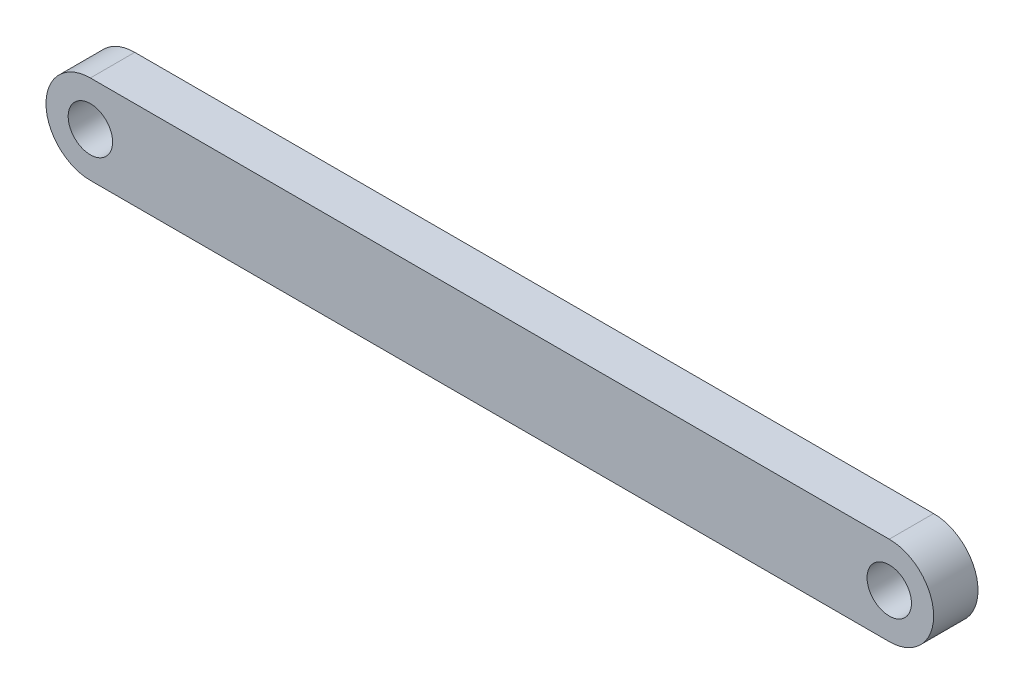
SolidWorks part; units mm, degrees
ref_plane "Front Plane" through (0, 0, 0) normal (0, 0, 1) x (1, 0, 0)
ref_plane "Top Plane" through (0, 0, 0) normal (0, 1, 0) x (1, 0, 0)
ref_plane "Right Plane" through (0, 0, 0) normal (1, 0, 0) x (0, 0, -1)
sketch "Sketch1" plane through (0, 0, 0) normal (0, 0, 1) x (1, 0, 0)
  line L0 (-22.86, 0) -> (22.86, 0) construction
  line L1 (-22.86, 2.54) -> (22.86, 2.54)
  line L2 (-22.86, -2.54) -> (22.86, -2.54)
  arc A0 (-22.86, 2.54) -> (-22.86, -2.54) centre (-22.86, 0) ccw
  arc A1 (22.86, -2.54) -> (22.86, 2.54) centre (22.86, 0) ccw
  circle A2 centre (-22.86, 0) radius 1.27
  circle A3 centre (22.86, 0) radius 1.27
  point P2 (0, 0)
  dimension "D2" = 2.54
  dimension "D3" = 2.54
  dimension "D1" = 45.72
extrude "Boss-Extrude1" add sketch "Sketch1" along normal blind 1.27 and the other way blind 1.27
